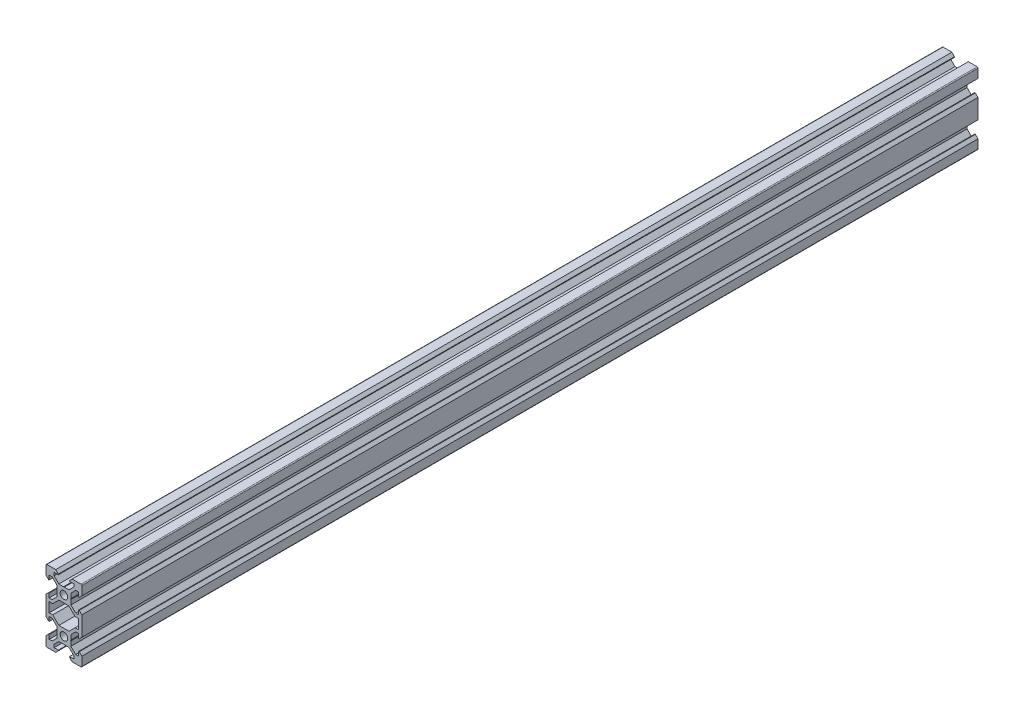
SolidWorks part; units mm, degrees
material "6061-T6 (SS)"
ref_plane "Front Plane" through (0, 0, 0) normal (0, 0, 1) x (1, 0, 0)
ref_plane "Top Plane" through (0, 0, 0) normal (0, 1, 0) x (1, 0, 0)
ref_plane "Right Plane" through (0, 0, 0) normal (1, 0, 0) x (0, 0, -1)
sketch "Sketch1" plane through (0, 0, 0) normal (0, 0, 1) x (1, 0, 0)
  line L0 (0, 0) -> (10, 0) construction
  line L1 (9.5, -20) -> (-9.5, -20)
  line L2 (10, -19.5) -> (10, 19.5)
  line L3 (9.5, 20) -> (-9.5, 20)
  line L4 (-10, -19.5) -> (-10, 19.5)
  line L5 (10, -20) -> (-10, 20) construction
  line L6 (10, 20) -> (-10, -20) construction
  circle A0 centre (0, 10) radius 2.1
  circle A1 centre (0, -10) radius 2.1
  arc A2 (-9.5, -20) -> (-10, -19.5) centre (-9.5, -19.5) cw
  arc A3 (9.5, -20) -> (10, -19.5) centre (9.5, -19.5) ccw
  arc A4 (10, 19.5) -> (9.5, 20) centre (9.5, 19.5) ccw
  arc A5 (-9.5, 20) -> (-10, 19.5) centre (-9.5, 19.5) ccw
  point P0 (0, 0)
  line B0 (0, 10) -> (0, 20) construction
  line B1 (0, 13.69) -> (-0.21, 13.9)
  line B2 (-0.21, 13.9) -> (-2.8393, 13.9)
  line B3 (-2.8393, 13.9) -> (-5.5, 16.5607)
  line B4 (-5.5, 16.5607) -> (-5.5, 18.2)
  line B5 (-5.5, 18.2) -> (-3.125, 18.2)
  line B6 (-3.125, 18.2) -> (-3.125, 18.545)
  line B7 (-3.125, 18.545) -> (-4.58, 20)
  line B8 (-4.58, 20) -> (4.58, 20)
  line B9 (0, 10) -> (-5.9132, 15.9132) construction
  line B10 (3.125, 18.545) -> (4.58, 20)
  line B11 (3.125, 18.2) -> (3.125, 18.545)
  line B12 (5.5, 18.2) -> (3.125, 18.2)
  line B13 (5.5, 16.5607) -> (5.5, 18.2)
  line B14 (2.8393, 13.9) -> (5.5, 16.5607)
  line B15 (0.21, 13.9) -> (2.8393, 13.9)
  line B16 (0, 13.69) -> (0.21, 13.9)
  line B17 (0, 10) -> (-10, 10) construction
  line B18 (-3.69, 10) -> (-3.9, 9.79)
  line B19 (-3.9, 9.79) -> (-3.9, 7.1607)
  line B20 (-3.9, 7.1607) -> (-6.5607, 4.5)
  line B21 (-6.5607, 4.5) -> (-8.2, 4.5)
  line B22 (-8.2, 4.5) -> (-8.2, 6.875)
  line B23 (-8.2, 6.875) -> (-8.545, 6.875)
  line B24 (-8.545, 6.875) -> (-10, 5.42)
  line B25 (-10, 5.42) -> (-10, 14.58)
  line B26 (0, 10) -> (-5.9132, 4.0868) construction
  line B27 (-8.545, 13.125) -> (-10, 14.58)
  line B28 (-8.2, 13.125) -> (-8.545, 13.125)
  line B29 (-8.2, 15.5) -> (-8.2, 13.125)
  line B30 (-6.5607, 15.5) -> (-8.2, 15.5)
  line B31 (-3.9, 12.8393) -> (-6.5607, 15.5)
  line B32 (-3.9, 10.21) -> (-3.9, 12.8393)
  line B33 (-3.69, 10) -> (-3.9, 10.21)
  line B34 (0, -10) -> (-10, -10) construction
  line B35 (-3.69, -10) -> (-3.9, -10.21)
  line B36 (-3.9, -10.21) -> (-3.9, -12.8393)
  line B37 (-3.9, -12.8393) -> (-6.5607, -15.5)
  line B38 (-6.5607, -15.5) -> (-8.2, -15.5)
  line B39 (-8.2, -15.5) -> (-8.2, -13.125)
  line B40 (-8.2, -13.125) -> (-8.545, -13.125)
  line B41 (-8.545, -13.125) -> (-10, -14.58)
  line B42 (-10, -14.58) -> (-10, -5.42)
  line B43 (0, -10) -> (-5.9132, -15.9132) construction
  line B44 (-8.545, -6.875) -> (-10, -5.42)
  line B45 (-8.2, -6.875) -> (-8.545, -6.875)
  line B46 (-8.2, -4.5) -> (-8.2, -6.875)
  line B47 (-6.5607, -4.5) -> (-8.2, -4.5)
  line B48 (-3.9, -7.1607) -> (-6.5607, -4.5)
  line B49 (-3.9, -9.79) -> (-3.9, -7.1607)
  line B50 (-3.69, -10) -> (-3.9, -9.79)
  line B51 (0, -10) -> (0, -20) construction
  line B52 (0, -13.69) -> (0.21, -13.9)
  line B53 (0.21, -13.9) -> (2.8393, -13.9)
  line B54 (2.8393, -13.9) -> (5.5, -16.5607)
  line B55 (5.5, -16.5607) -> (5.5, -18.2)
  line B56 (5.5, -18.2) -> (3.125, -18.2)
  line B57 (3.125, -18.2) -> (3.125, -18.545)
  line B58 (3.125, -18.545) -> (4.58, -20)
  line B59 (4.58, -20) -> (-4.58, -20)
  line B60 (0, -10) -> (5.9132, -15.9132) construction
  line B61 (-3.125, -18.545) -> (-4.58, -20)
  line B62 (-3.125, -18.2) -> (-3.125, -18.545)
  line B63 (-5.5, -18.2) -> (-3.125, -18.2)
  line B64 (-5.5, -16.5607) -> (-5.5, -18.2)
  line B65 (-2.8393, -13.9) -> (-5.5, -16.5607)
  line B66 (-0.21, -13.9) -> (-2.8393, -13.9)
  line B67 (0, -13.69) -> (-0.21, -13.9)
  line B68 (0, -10) -> (10, -10) construction
  line B69 (3.69, -10) -> (3.9, -9.79)
  line B70 (3.9, -9.79) -> (3.9, -7.1607)
  line B71 (3.9, -7.1607) -> (6.5607, -4.5)
  line B72 (6.5607, -4.5) -> (8.2, -4.5)
  line B73 (8.2, -4.5) -> (8.2, -6.875)
  line B74 (8.2, -6.875) -> (8.545, -6.875)
  line B75 (8.545, -6.875) -> (10, -5.42)
  line B76 (10, -5.42) -> (10, -14.58)
  line B77 (0, -10) -> (5.9132, -4.0868) construction
  line B78 (8.545, -13.125) -> (10, -14.58)
  line B79 (8.2, -13.125) -> (8.545, -13.125)
  line B80 (8.2, -15.5) -> (8.2, -13.125)
  line B81 (6.5607, -15.5) -> (8.2, -15.5)
  line B82 (3.9, -12.8393) -> (6.5607, -15.5)
  line B83 (3.9, -10.21) -> (3.9, -12.8393)
  line B84 (3.69, -10) -> (3.9, -10.21)
  line B85 (0, 10) -> (10, 10) construction
  line B86 (3.69, 10) -> (3.9, 10.21)
  line B87 (3.9, 10.21) -> (3.9, 12.8393)
  line B88 (3.9, 12.8393) -> (6.5607, 15.5)
  line B89 (6.5607, 15.5) -> (8.2, 15.5)
  line B90 (8.2, 15.5) -> (8.2, 13.125)
  line B91 (8.2, 13.125) -> (8.545, 13.125)
  line B92 (8.545, 13.125) -> (10, 14.58)
  line B93 (10, 14.58) -> (10, 5.42)
  line B94 (0, 10) -> (5.9132, 15.9132) construction
  line B95 (8.545, 6.875) -> (10, 5.42)
  line B96 (8.2, 6.875) -> (8.545, 6.875)
  line B97 (8.2, 4.5) -> (8.2, 6.875)
  line B98 (6.5607, 4.5) -> (8.2, 4.5)
  line B99 (3.9, 7.1607) -> (6.5607, 4.5)
  line B100 (3.9, 9.79) -> (3.9, 7.1607)
  line B101 (3.69, 10) -> (3.9, 9.79)
  line B102 (-8.2, -2.7) -> (-8.2, 2.7)
  line B103 (-8.2, 2.7) -> (-6.2393, 2.7)
  line B104 (-6.2393, 2.7) -> (-2.8393, 6.1)
  line B105 (-2.8393, 6.1) -> (2.8393, 6.1)
  line B106 (0, 6.1) -> (0, 0) construction
  line B107 (0, 0) -> (-8.2, 0) construction
  line B108 (6.2393, 2.7) -> (2.8393, 6.1)
  line B109 (8.2, 2.7) -> (6.2393, 2.7)
  line B110 (8.2, -2.7) -> (8.2, 2.7)
  line B111 (8.2, -2.7) -> (6.2393, -2.7)
  line B112 (6.2393, -2.7) -> (2.8393, -6.1)
  line B113 (-2.8393, -6.1) -> (2.8393, -6.1)
  line B114 (-6.2393, -2.7) -> (-2.8393, -6.1)
  line B115 (-8.2, -2.7) -> (-6.2393, -2.7)
  line B116 (0, 6.1) -> (0, 10) construction
  line B117 (0, 10) -> (-5.0927, 4.9073) construction
  dimension "D4" = 4.2
  dimension "D5" = 0.5
  dimension "D1" = 20
  dimension "D2" = 40
  dimension "D3" = 20
sketch_block_instance "V Slot 1-4"
sketch_block "V Slot 1" parameters "D1"=10, "D2"=11, "D3"=4.3, "D4"=1.8, "D5"=0.21, "D6"=45, "D7"=9.16, "D8"=1.5, "D9"=6.25
sketch_block_instance "V Slot 1-5"
sketch_block_instance "V Slot 1-6"
sketch_block_instance "V Slot 1-7"
sketch_block_instance "V Slot 1-8"
sketch_block_instance "V Slot 1-9"
sketch_block_instance "Center Cutout 1-1"
sketch_block "Center Cutout 1" parameters "D1"=5.4, "D2"=12.2, "D3"=8.2, "D4"=45, "D5"=10, "D6"=1.5
extrude "Boss-Extrude1" add sketch "Sketch1" along normal blind 500 contours B101 B86 B87 B88 B89 B90 B91 B92 L2 A4 L3 B10 B11 B12 B13 B14 B15 B16 B1 B2 B3 B4 B5 B6 B7 A5 L4 B27 B28 B29 B30 B31 B32 B33 B18 B19 B20 B21 B22 B23 B24 B44 B45 B46 B47 B48 B49 B50 B35 region at (7.04, -19.5528, 0)
ref_plane "Upper Plane" through (0, 10, 0) normal (0, 1, 0) x (1, 0, 0)
ref_plane "Lower Plane" through (0, -10, 0) normal (0, 1, 0) x (1, 0, 0)
